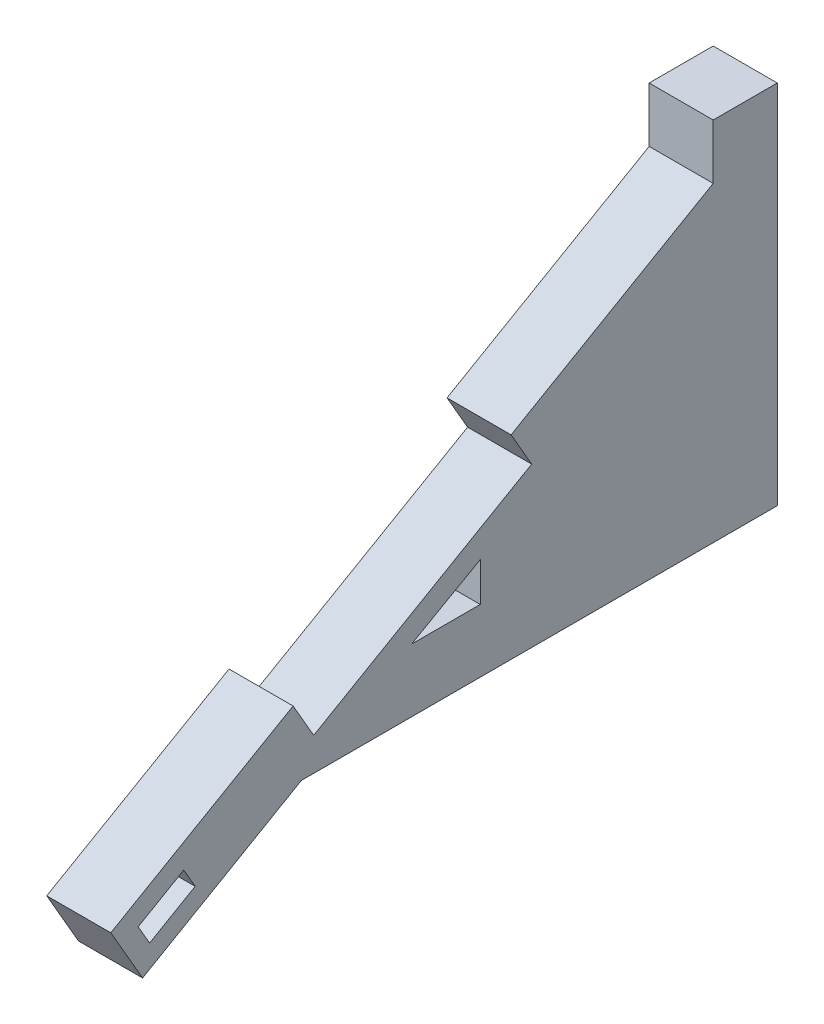
SolidWorks part; units mm, degrees
ref_plane "Front Plane" through (0, 0, 0) normal (0, 0, 1) x (1, 0, 0)
ref_plane "Top Plane" through (0, 0, 0) normal (0, 1, 0) x (1, 0, 0)
ref_plane "Right Plane" through (0, 0, 0) normal (1, 0, 0) x (0, 0, -1)
sketch "Sketch1" plane through (0, 0, 0) normal (1, 0, 0) x (0, 0, -1)
  line L0 (0, 0) -> (0, 40)
  line L1 (0, 40) -> (-7, 40)
  line L2 (-7, 40) -> (-7, 34)
  line L3 (-7, 34) -> (-29.0836, 21.25)
  line L4 (-29.0836, 21.25) -> (-26.8336, 17.3529)
  line L5 (-26.8336, 17.3529) -> (-50.6493, 3.6029)
  line L6 (-50.6493, 3.6029) -> (-52.8993, 7.5)
  line L7 (-52.8993, 7.5) -> (-72.8179, -4)
  line L8 (-72.8179, -4) -> (-69.3455, -10.0144)
  line L9 (-69.3455, -10.0144) -> (-52, 0)
  line L10 (-52, 0) -> (0, 0)
  line L11 (-69.8283, -4.9261) -> (-64.8487, -2.0511)
  line L12 (-64.8487, -2.0511) -> (-63.5987, -4.2162)
  line L13 (-63.5987, -4.2162) -> (-68.5783, -7.0912)
  line L14 (-68.5783, -7.0912) -> (-69.8283, -4.9261)
  line L15 (-39.9499, 6.884) -> (-32.4499, 11.134)
  line L16 (-32.4499, 11.134) -> (-32.4499, 6.884)
  line L17 (-32.4499, 6.884) -> (-39.9499, 6.884)
  dimension "D1" = 40
  dimension "D2" = 7
  dimension "D3" = 6
  dimension "D4" = 25.5
  dimension "D5" = 4.5
  dimension "D6" = 27.5
  dimension "D7" = 4.5
  dimension "D8" = 23
  dimension "D9" = 52
  dimension "D10" = 150
  dimension "D11" = 2.148
  dimension "D12" = 2.126
  dimension "D13" = 2.5
  dimension "D14" = 5.75
  dimension "D15" = 7.5
  dimension "D16" = 4.25
  dimension "D17" = 32.868
  dimension "D18" = 6.884
extrude "Boss-Extrude1" add sketch "Sketch1" against normal blind 7
